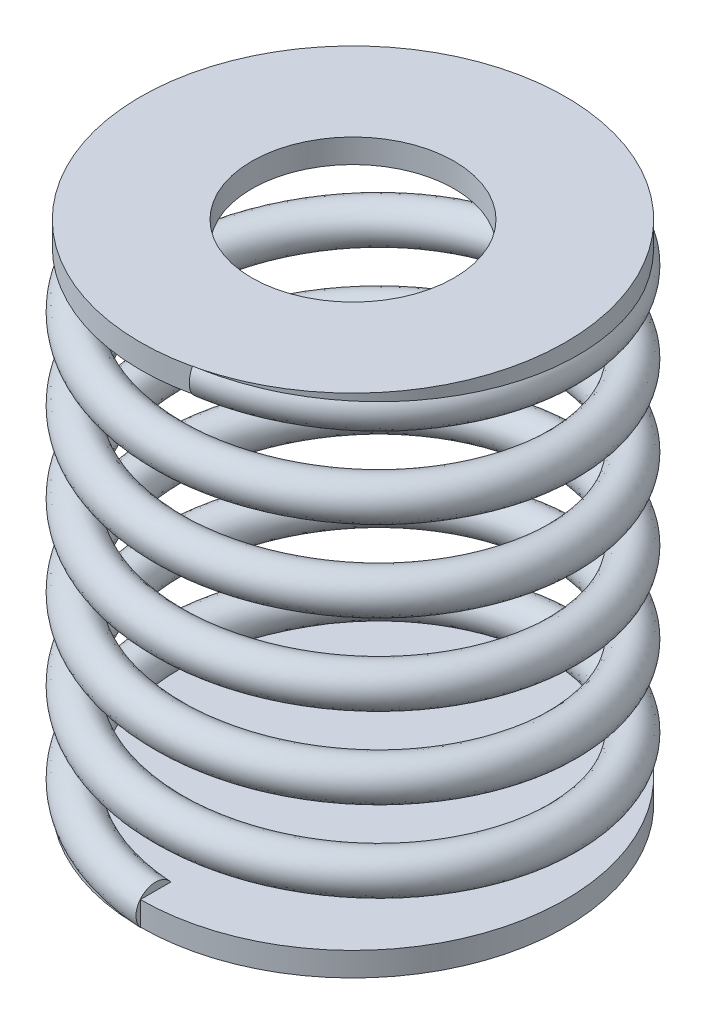
SolidWorks part; units mm, degrees
ref_plane "Front Plane" through (0, 0, 0) normal (0, 0, 1) x (1, 0, 0)
ref_plane "Top Plane" through (0, 0, 0) normal (0, 1, 0) x (1, 0, 0)
ref_plane "Right Plane" through (0, 0, 0) normal (1, 0, 0) x (0, 0, -1)
sketch "Sketch5" plane through (0, 0, 0) normal (0, 1, 0) x (1, 0, 0)
  circle A0 centre (0, 0) radius 12.4
  dimension "D1" = 24.8
curve "Helix/Spiral2" pitch 5.08 height 30.3 radius 12.4 left hand yes centre (0, 0, 0) axis (0, 1, 0) start towards (0, 0, 1)
ref_plane "Plane1" through (0, 0, 0) normal (1, 0, 0) x (0, 0, -1)
sketch "Sketch8" plane through (0, 0, 0) normal (0, 1, 0) x (1, 0, 0)
  circle A0 centre (0, 0) radius 13.35
  dimension "D1" = 26.7
extrude "Boss-Extrude1" add sketch "Sketch8" along normal mid plane 1.5 contours A0
extrude "Boss-Extrude2" add sketch "Sketch8<3>" along normal blind 1.5 from offset 29.55 contours A0
sketch "Sketch8<3>" plane through (0, 0, 0) normal (0, 1, 0) x (1, 0, 0) same geometry as "Sketch8"
sketch "Sketch10" plane through (0, 0, 0) normal (1, 0, 0) x (0, 0, -1)
  circle A0 centre (-12.4, 0) radius 1.225
  dimension "D1" = 2.45
sweep "Sweep2" add profiles "Sketch10" path "Helix/Spiral2"
sketch "Sketch12" plane through (0, 31.05, 0) normal (0, 1, 0) x (1, 0, 0)
  circle A0 centre (0, 0) radius 13.35
extrude "Cut-Extrude5" cut sketch "Sketch5<3>" against normal blind 1.5 contours A0 region at (0, 0, 0)
sketch "Sketch5<3>" plane through (0, 0, 0) normal (0, 1, 0) x (1, 0, 0) same geometry as "Sketch5"
extrude "Cut-Extrude6" cut sketch "Sketch12" along normal blind 1.5
sketch "Sketch14" plane through (0, -0.75, 0) normal (0, -1, 0) x (1, 0, 0)
  circle A0 centre (0, 0) radius 13.35
extrude "Cut-Extrude7" cut sketch "Sketch14" along normal blind 2.5
sketch "Sketch15" plane through (0, 31.05, 0) normal (0, 1, 0) x (1, 0, 0)
  circle A0 centre (0, 0) radius 6.35
  dimension "D1" = 12.7
extrude "Cut-Extrude8" cut sketch "Sketch15" against normal blind 10
